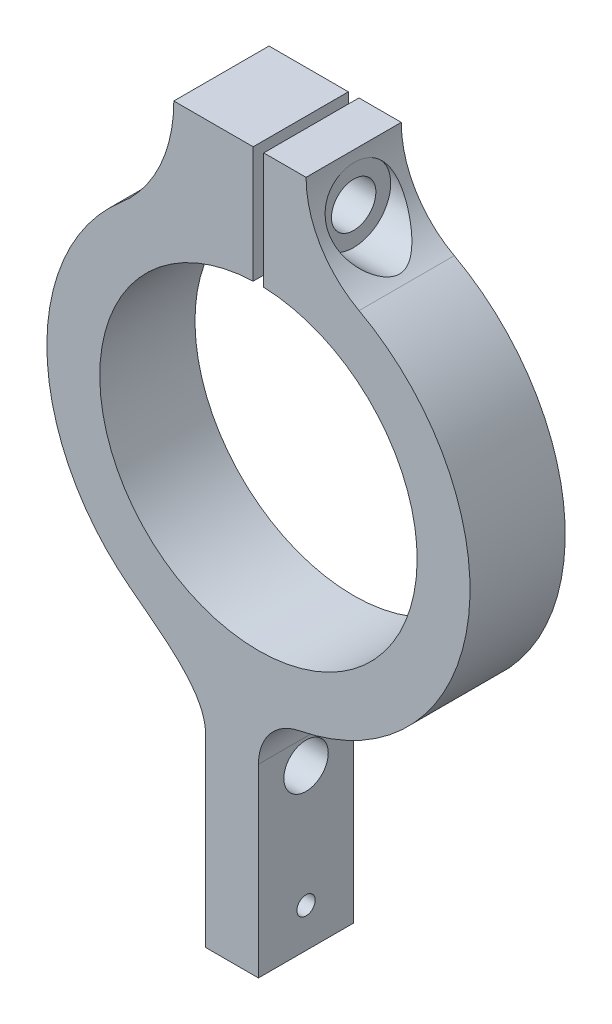
SolidWorks part; units mm, degrees
material "6061-T6 (SS)"
ref_plane "Front Plane" through (0, 0, 0) normal (0, 0, 1) x (1, 0, 0)
ref_plane "Top Plane" through (0, 0, 0) normal (0, 1, 0) x (1, 0, 0)
ref_plane "Right Plane" through (0, 0, 0) normal (1, 0, 0) x (0, 0, -1)
sketch "Sketch1" plane through (0, 0, 0) normal (0, 0, 1) x (1, 0, 0)
  line L0 (0, 0) -> (0, 40) construction
  line L1 (0, -48.6004) -> (0, -83.6004)
  line L2 (0, -83.6004) -> (-10, -83.6004)
  line L3 (-10, -83.6004) -> (-10, -48.6004)
  line L4 (30, 0) -> (40, 0) construction
  line L6 (0, 40) -> (0, 52) construction
  line L7 (0, 52) -> (1, 52) construction
  line L8 (1, 52) -> (1, 29.9833)
  line L9 (1, 52) -> (9, 52)
  line L11 (0, 52) -> (-1, 52) construction
  line L12 (-1, 52) -> (-1, 29.9833)
  line L13 (-1, 52) -> (-16, 52)
  arc A0 (-1, 29.9833) -> (1, 29.9833) centre (0, 0) ccw
  arc A1 (0, -48.6004) -> (7.6931, -39.2532) centre (9.525, -48.6004) cw
  arc A2 (0, 40) -> (-1, 39.9875) centre (0, 0) ccw construction
  arc A3 (9, 52) -> (19.0232, 35.1869) centre (28.1129, 52) ccw
  arc A4 (-25.9512, 30.439) -> (-26.5352, -29.9313) centre (0, 0) ccw
  circle A5 centre (0, 0) radius 40 construction
  arc A6 (-25.9512, 30.439) -> (-16, 52) centre (-44.3333, 52) ccw
  arc A8 (7.6931, -39.2532) -> (19.0232, 35.1869) centre (0, 0) ccw
  spline S0 degree 3 poles (-26.5352, -29.9313) (-20.9482, -34.8844) (-10, -40.904) (-10, -48.6004) knots 0 0 0 0 1 1 1 1
  point P27 (0, -40)
  dimension "D1" = 60
  dimension "D3" = 35
  dimension "D4" = 10
  dimension "D2" = 10
  dimension "D11" = 9.525
  dimension "D6" = 12
  dimension "D7" = 1
  dimension "D8" = 8
  dimension "D9" = 1
  dimension "D10" = 15
extrude "main body" add sketch "Sketch1" along normal blind 18
sketch "Sketch7" plane through (1, 0, 0) normal (-1, 0, 0) x (0, 0, 1)
  line L3 (9, 43) -> (9, 52) construction
  line L4 (18, 52) -> (0, 52) construction
  line L5 (9, 43) -> (0, 43) construction
  line L6 (0, 52) -> (0, 35.1869) construction
  circle A0 centre (9, 43) radius 4
  dimension "D1" = 8
sketch "Sketch12" plane through (0, 0, 0) normal (1, 0, 0) x (0, 0, -1)
  circle A0 centre (-9, -53.34) radius 4
  circle A1 centre (-9, -53.34) radius 7 construction
  circle A2 centre (-9, -76.2) radius 4
  circle A3 centre (-9, -76.2) radius 7 construction
  dimension "D1" = 8
  dimension "D2" = 14
  dimension "D3" = 14
  dimension "D4" = 8
  dimension "D6" = 22.86
  dimension "D5" = 76.2
hole_wizard "M8 Clearance Hole1" positions "Sketch13" profile "Sketch14" hole size "M8" standard "ANSI Metric" end condition through all
sketch "Sketch13" plane through (1, 0, 0) normal (-1, 0, 0) x (0, 0, 1)
  point P0 (9, 43)
sketch "Sketch14" plane through (1, 43, 9) normal (0, 1, 0) x (0, 0, 1)
  line L0 (0, 0) -> (0, 39)
  line L1 (0, 39) -> (4.2, 39)
  line L2 (4.2, 39) -> (4.2, 0)
  line L5 (4.2, 0) -> (0, 0)
  line L11 (0, -6.35) -> (0, 107.95) construction
  dimension "Thru Hole Dia." = 8.4
  dimension "Thru Hole Depth" = 39
hole_wizard "M8 Clearance Hole2" positions "Sketch15" profile "Sketch16" hole size "M8" standard "ANSI Metric" end condition through all
sketch "Sketch15" plane through (1, 0, 0) normal (-1, 0, 0) x (0, 0, 1)
  point P0 (9, 43)
sketch "Sketch16" plane through (1, 43, 9) normal (0, 1, 0) x (0, 0, -1)
  line L0 (0, 0) -> (0, 41)
  line L1 (0, 41) -> (4.2, 41)
  line L2 (4.2, 41) -> (4.2, 0)
  line L5 (4.2, 0) -> (0, 0)
  line L11 (0, -6.35) -> (0, 107.95) construction
  dimension "Thru Hole Dia." = 8.4
  dimension "Thru Hole Depth" = 41
sketch "Sketch17" plane through (0, 0, 18) normal (0, 0, 1) x (1, 0, 0)
  line L0 (-16, 52) -> (-16, 25.3772)
  line L1 (9, 52) -> (9, 28.6182)
  arc A0 (-1, 29.9833) -> (1, 29.9833) centre (0, 0) ccw construction
hole_wizard "M8 Clearance Hole3" positions "Sketch18" profile "Sketch19" hole size "M8" standard "ANSI Metric" end condition through all
sketch "Sketch18" plane through (0, 0, 0) normal (1, 0, 0) x (0, 0, -1)
  point P0 (-9, -53.34)
sketch "Sketch19" plane through (0, -53.34, 9) normal (0, 1, 0) x (0, 0, -1)
  line L0 (0, 0) -> (0, 40)
  line L1 (0, 40) -> (4.2, 40)
  line L2 (4.2, 40) -> (4.2, 0)
  line L5 (4.2, 0) -> (0, 0)
  line L11 (0, -6.35) -> (0, 107.95) construction
  dimension "Thru Hole Dia." = 8.4
  dimension "Thru Hole Depth" = 40
ref_plane "Plane1" through (-16, 0, 0) normal (-1, 0, 0) x (0, 0, 1)
sketch "Sketch26" plane through (-16, 0, 0) normal (-1, 0, 0) x (0, 0, 1)
  circle A0 centre (9, 43) radius 7
  dimension "D1" = 14
ref_plane "Plane2" through (9, 0, 0) normal (1, 0, 0) x (0, 0, -1)
sketch "Sketch27" plane through (9, 0, 0) normal (1, 0, 0) x (0, 0, -1)
  circle A0 centre (-9, 43) radius 7
  circle A1 centre (-9, 43) radius 7 construction
extrude "Cut-Extrude2" cut sketch "Sketch27" along normal through all
sketch "Sketch29" plane through (0, 0, 18) normal (0, 0, 1) x (1, 0, 0)
  line L0 (-16, 52) -> (-42.54, 52) construction
  line L1 (-42.54, 52) -> (-42.54, 0) construction
  line L2 (-42.54, 0) -> (-40, 0) construction
  arc A0 (-25.9512, 30.439) -> (-26.5352, -29.9313) centre (0, 0) ccw construction
  dimension "D1" = 2.54
hole_wizard "#8-32 Tapped Hole1" positions "Sketch30" profile "Sketch32" tap size "#8-32" standard "ANSI Inch" end condition through all
sketch "Sketch30" plane through (0, 0, 0) normal (1, 0, 0) x (0, 0, -1)
  point P0 (-9, -76.2)
sketch "Sketch32" plane through (0, -76.2, 9) normal (0, 1, 0) x (0, 0, -1)
  line L0 (0, 0) -> (0, 40)
  line L1 (0, 40) -> (1.7272, 40)
  line L2 (1.7272, 40) -> (1.7272, 0)
  line L5 (1.7272, 0) -> (0, 0)
  line L11 (0, -6.35) -> (0, 107.95) construction
  dimension "Thru Tap Drill Dia." = 3.4544
  dimension "Thru Tap Drill Depth" = 40
cosmetic thread "Hole Thread1" parameters "D2"=4.1656
